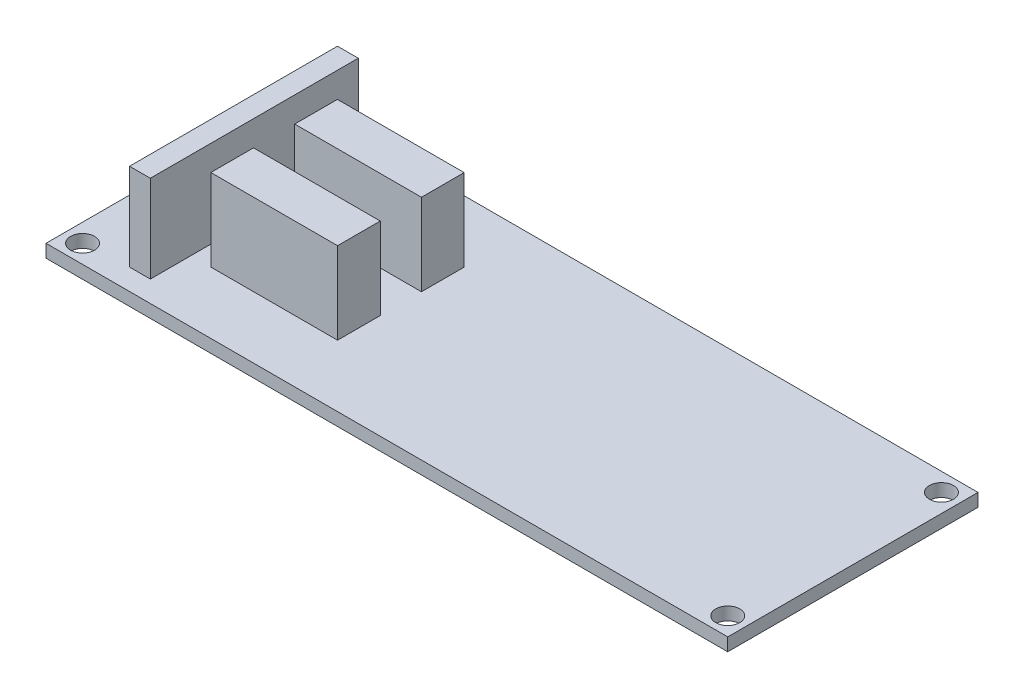
SolidWorks part; units mm, degrees
material "Glass Epoxy Composite"
ref_plane "Front Plane" through (0, 0, 0) normal (0, 0, 1) x (1, 0, 0)
ref_plane "Top Plane" through (0, 0, 0) normal (0, 1, 0) x (1, 0, 0)
ref_plane "Right Plane" through (0, 0, 0) normal (1, 0, 0) x (0, 0, -1)
sketch "Sketch1" plane through (0, 0, 0) normal (0, 1, 0) x (1, 0, 0)
  line L1 (-41.6369, -15.2844) -> (41.637, -15.2844)
  line L2 (-41.6369, -15.2844) -> (-41.6369, 15.2845)
  line L3 (-41.6369, 15.2845) -> (41.637, 15.2845)
  line L4 (41.637, -15.2844) -> (41.637, 15.2845)
  line L5 (-41.6369, -15.2844) -> (41.637, 15.2845) construction
  line L6 (-41.6369, 15.2845) -> (41.637, -15.2844) construction
  point P0 (0, 0)
  dimension "D1" = 30.5689
  dimension "D2" = 83.2739
extrude "Proton PCB " add sketch "Sketch1" along normal blind 1.5811
sketch "Sketch2" plane through (0, 1.5811, 0) normal (0, 1, 0) x (1, 0, 0)
  line L0 (-41.6369, 15.2845) -> (-41.6369, -15.2844) construction
  line L1 (-29.0575, 2.5164) -> (-13.5764, 2.5164)
  line L6 (-29.0575, 2.5164) -> (-29.0575, 7.7325)
  line L7 (-29.0575, 7.7325) -> (-13.5764, 7.7325)
  line L8 (-13.5764, 2.5164) -> (-13.5764, 7.7325)
  line L9 (-29.0575, 2.5164) -> (-13.5764, 7.7325) construction
  line L10 (-29.0575, 7.7325) -> (-13.5764, 2.5164) construction
  line L11 (41.637, 15.2845) -> (-41.6369, 15.2845) construction
  line L12 (0, 0) -> (-41.6369, 0) construction
  line L13 (-29.0575, -7.7325) -> (-13.5764, -7.7325)
  line L14 (-13.5764, -2.5164) -> (-13.5764, -7.7325)
  line L15 (-29.0575, -2.5164) -> (-13.5764, -2.5164)
  line L16 (-29.0575, -2.5164) -> (-29.0575, -7.7325)
  point P0 (-21.3169, 5.1245)
  point P3 (-22.0462, 3.81)
  dimension "D1" = 5.2161
  dimension "D2" = 15.4812
  dimension "D3" = 20.32
  dimension "D4" = 10.16
extrude "JST 6 pin Connectors" add sketch "Sketch2" along normal blind 10
sketch "Sketch3" plane through (0, 1.5811, 0) normal (0, 1, 0) x (1, 0, 0)
  line L0 (0, 0) -> (-41.6369, 0) construction
  line L1 (-31.4769, 12.7) -> (-34.0169, 12.7)
  line L2 (-31.4769, 12.7) -> (-31.4769, -12.7)
  line L3 (-31.4769, -12.7) -> (-34.0169, -12.7)
  line L4 (-34.0169, 12.7) -> (-34.0169, -12.7)
  line L5 (-31.4769, 12.7) -> (-34.0169, -12.7) construction
  line L6 (-31.4769, -12.7) -> (-34.0169, 12.7) construction
  line L7 (-41.6369, 15.2845) -> (-41.6369, -15.2844) construction
  point P0 (-32.7469, 0)
  dimension "D1" = 25.4
  dimension "D2" = 2.54
  dimension "D3" = 10.16
extrude "Boss-Extrude1" add sketch "Sketch3" along normal blind 10.668
sketch "Sketch4" plane through (0, 1.5811, 0) normal (0, 1, 0) x (1, 0, 0)
  line L14 (-39.4033, 13.0508) -> (-39.4033, -13.0508)
  line L15 (-39.4033, -13.0508) -> (39.4033, -13.0508)
  line L16 (39.4033, -13.0508) -> (39.4033, 13.0508)
  line L17 (39.4033, 13.0508) -> (-39.4033, 13.0508)
  line L18 (-39.4033, 13.0508) -> (-39.4033, -13.0508) construction
  line L19 (-39.4033, -13.0508) -> (39.4033, -13.0508) construction
  line L20 (39.4033, -13.0508) -> (39.4033, 13.0508) construction
  line L21 (39.4033, 13.0508) -> (-39.4033, 13.0508) construction
  circle A0 centre (-39.4033, 13.0508) radius 1.4653
  circle A1 centre (39.4033, 13.0508) radius 1.4653
  circle A2 centre (-39.4033, -13.0508) radius 1.4653
  circle A3 centre (39.4033, -13.0508) radius 1.4653
  dimension "D2" = 2.9305
  dimension "D1" = 2.2336
extrude "Cut-Extrude1" cut sketch "Sketch4" against normal up to surface (1.5812 mm away) up to face at (0, 0, 0)
sketch "Sketch5" plane through (0, 0, 0) normal (0, -1, 0) x (1, 0, 0)
  line L0 (0, 0) -> (-41.6369, 0) construction
  line L7 (-22.8409, 7.6644) -> (-18.2689, 7.6644)
  line L8 (-22.8409, 7.6644) -> (-22.8409, 11.2204)
  line L9 (-22.8409, 11.2204) -> (-18.2689, 11.2204)
  line L10 (-18.2689, 7.6644) -> (-18.2689, 11.2204)
  line L11 (-22.8409, 7.6644) -> (-18.2689, 11.2204) construction
  line L12 (-22.8409, 11.2204) -> (-18.2689, 7.6644) construction
  line L13 (-28.1749, 7.6644) -> (-23.6029, 7.6644)
  line L14 (-28.1749, 7.6644) -> (-28.1749, 11.2204)
  line L15 (-28.1749, 11.2204) -> (-23.6029, 11.2204)
  line L16 (-23.6029, 7.6644) -> (-23.6029, 11.2204)
  line L17 (-28.1749, 7.6644) -> (-23.6029, 11.2204) construction
  line L18 (-28.1749, 11.2204) -> (-23.6029, 7.6644) construction
  line L19 (-17.5069, 7.6644) -> (-12.9349, 7.6644)
  line L20 (-17.5069, 7.6644) -> (-17.5069, 11.2204)
  line L21 (-17.5069, 11.2204) -> (-12.9349, 11.2204)
  line L22 (-12.9349, 7.6644) -> (-12.9349, 11.2204)
  line L23 (-17.5069, 7.6644) -> (-12.9349, 11.2204) construction
  line L24 (-17.5069, 11.2204) -> (-12.9349, 7.6644) construction
  line L25 (21.317, -4.6165) -> (25.889, -4.6165)
  line L26 (21.317, -4.6165) -> (21.317, -1.0605)
  line L27 (21.317, -1.0605) -> (25.889, -1.0605)
  line L28 (25.889, -4.6165) -> (25.889, -1.0605)
  line L29 (21.317, -4.6165) -> (25.889, -1.0605) construction
  line L30 (21.317, -1.0605) -> (25.889, -4.6165) construction
  line L31 (-41.6369, -15.2845) -> (-41.6369, 15.2844) construction
  line L32 (-41.6369, 15.2844) -> (41.637, 15.2844) construction
  line L33 (-12.9349, -7.6644) -> (-12.9349, -11.2204)
  line L34 (-17.5069, -11.2204) -> (-12.9349, -11.2204)
  line L35 (-17.5069, -7.6644) -> (-17.5069, -11.2204)
  line L36 (-17.5069, -7.6644) -> (-12.9349, -7.6644)
  line L37 (-22.8409, -7.6644) -> (-18.2689, -7.6644)
  line L38 (-18.2689, -7.6644) -> (-18.2689, -11.2204)
  line L39 (-22.8409, -11.2204) -> (-18.2689, -11.2204)
  line L40 (-22.8409, -7.6644) -> (-22.8409, -11.2204)
  line L41 (-23.6029, -7.6644) -> (-23.6029, -11.2204)
  line L42 (-28.1749, -11.2204) -> (-23.6029, -11.2204)
  line L43 (-28.1749, -7.6644) -> (-28.1749, -11.2204)
  line L44 (-28.1749, -7.6644) -> (-23.6029, -7.6644)
  line L45 (41.637, 15.2844) -> (41.637, -15.2845) construction
  line L46 (41.637, -15.2845) -> (-41.6369, -15.2845) construction
  point P0 (-2.5981, 8.1672)
  point P5 (-20.5549, 9.4424)
  point P10 (-25.8889, 9.4424)
  point P15 (-15.2209, 9.4424)
  point P20 (23.603, -2.8385)
  dimension "D1" = 4.572
  dimension "D2" = 3.556
  dimension "D3" = 15.24
  dimension "D4" = 0.762
  dimension "D5" = 7.62
  dimension "D6" = 28.702
  dimension "D7" = 20.32
  dimension "D8" = 14.224
extrude "Boss-Extrude2" add sketch "Sketch5" along normal blind 1.778
sketch "Sketch6" plane through (0, 0, 0) normal (0, -1, 0) x (1, 0, 0)
  line L0 (-41.6369, -15.2845) -> (-41.6369, 15.2844) construction
  line L1 (-11.1569, 3.3464) -> (6.6231, 3.3464)
  line L2 (-11.1569, 3.3464) -> (-11.1569, 10.2044)
  line L3 (-11.1569, 10.2044) -> (6.6231, 10.2044)
  line L4 (6.6231, 3.3464) -> (6.6231, 10.2044)
  line L5 (-11.1569, 3.3464) -> (6.6231, 10.2044) construction
  line L6 (-11.1569, 10.2044) -> (6.6231, 3.3464) construction
  line L7 (-41.6369, 15.2844) -> (41.637, 15.2844) construction
  point P0 (-2.2669, 6.7755)
  dimension "D1" = 17.78
  dimension "D2" = 6.858
  dimension "D3" = 48.26
  dimension "D4" = 11.938
extrude "Boss-Extrude3" add sketch "Sketch6" along normal blind 2.794
